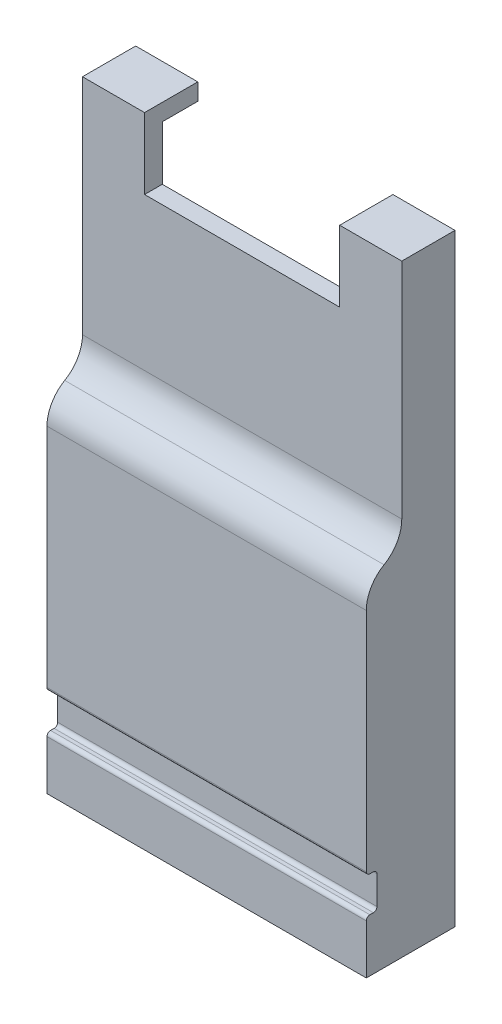
SolidWorks part; units mm, degrees
ref_plane "前视基准面" through (0, 0, 0) normal (0, 0, 1) x (1, 0, 0)
ref_plane "上视基准面" through (0, 0, 0) normal (0, 1, 0) x (1, 0, 0)
ref_plane "右视基准面" through (0, 0, 0) normal (1, 0, 0) x (0, 0, -1)
other "Configuration Table"
sketch "草图1" plane through (0, 0, 0) normal (0, 0, 1) x (1, 0, 0)
  line L1 (-45, -85) -> (45, -85)
  line L2 (-45, -85) -> (-45, 85)
  line L3 (-45, 85) -> (45, 85)
  line L4 (45, -85) -> (45, 85)
  line L5 (-45, -85) -> (45, 85) construction
  line L6 (-45, 85) -> (45, -85) construction
  point P0 (0, 0)
  dimension "D1" = 90
  dimension "D2" = 170
extrude "凸台-拉伸1" add sketch "草图1" along normal blind 25
sketch "草图2" plane through (0, 0, 25) normal (0, 0, 1) x (1, 0, 0)
  line L0 (-45, 85) -> (-45, -85) construction
  line L1 (45, 85) -> (-45, 85)
  line L2 (45, 85) -> (45, 14.7077)
  line L3 (45, 14.7077) -> (-45, 14.7077)
  line L4 (-45, 85) -> (-45, 14.7077)
extrude "切除-拉伸1" cut sketch "草图2" against normal blind 10
fillet "圆角1" radius 10 1 edges at (0, 14.7077, 25)
fillet "圆角2" radius 10 1 edges at (0, 14.7077, 15)
sketch "草图3" plane through (0, 0, 0) normal (0, 0, -1) x (-1, 0, 0)
  line L0 (45, 85) -> (45, -85) construction
  line L1 (-40.25, -85) -> (40.25, -85)
  line L2 (-40.25, -85) -> (-40.25, 80.25)
  line L3 (-40.25, 80.25) -> (40.25, 80.25)
  line L4 (40.25, -85) -> (40.25, 80.25)
  line L5 (45, -85) -> (-45, -85) construction
  point P0 (0, 0)
  point P6 (0, 0)
  point P7 (0, 0)
  point P10 (40.25, -85)
  dimension "D1" = 4.75
  dimension "D2" = 80.5
extrude "切除-拉伸2" cut sketch "草图3" against normal blind 10
sketch "草图5" plane through (40.25, 0, 0) normal (-1, 0, 0) x (0, 0, 1)
  line L0 (8.8, 80.25) -> (8.8, -85)
  line L3 (10, 80.25) -> (0, 80.25) construction
  line L4 (10, -85) -> (0, -85) construction
  line L5 (8.8, -85) -> (8.2, -85)
  line L6 (8.2, -85) -> (8.2, 80.25)
  line L7 (8.2, 80.25) -> (8.8, 80.25)
  line L8 (10, 80.25) -> (10, -85) construction
  dimension "D1" = 1.2
  dimension "D2" = 0.6
extrude "凸台-拉伸2" add sketch "草图5" along normal blind 0.9
sketch "草图6" plane through (-40.25, 0, 0) normal (1, 0, 0) x (0, 0, -1)
  line L0 (-8.8, 80.25) -> (-8.8, -85)
  line L3 (-9.4, -85) -> (-9.4, 80.25)
  line L4 (-9.4, 80.25) -> (-8.8, 80.25)
  line L5 (-10, -85) -> (-10, 80.25) construction
  line L6 (-9.4, -85) -> (-8.8, -85)
  dimension "D1" = 1.2
  dimension "D2" = 0.6
extrude "凸台-拉伸3" add sketch "草图6" along normal blind 0.9 contours L0 L6 L3 L4
sketch "草图9" plane through (0, 0, 25) normal (0, 0, 1) x (1, 0, 0)
  line L0 (-45, 4.7077) -> (-45, -85) construction
  line L1 (-45, -70.0642) -> (45, -70.0642)
  line L2 (-45, -70.0642) -> (-45, -60.0642)
  line L3 (-45, -60.0642) -> (45, -60.0642)
  line L4 (45, -70.0642) -> (45, -60.0642)
  line L5 (45, -85) -> (45, 4.7077) construction
  dimension "D1" = 10
extrude "切除-拉伸5" cut sketch "草图9" against normal blind 3
fillet "圆角8" radius 1 2 edges at (0, -60.0642, 22) (0, -60.0642, 25)
fillet "圆角9" radius 1 2 edges at (0, -70.0642, 25) (0, -70.0642, 22)
sketch "草图10" plane through (0, 0, 15) normal (0, 0, 1) x (1, 0, 0)
  line L0 (45, 85) -> (-45, 85) construction
  line L1 (-27.5, 105) -> (27.5, 105)
  line L2 (-27.5, 105) -> (-27.5, 65)
  line L3 (-27.5, 65) -> (27.5, 65)
  line L4 (27.5, 105) -> (27.5, 65)
  line L5 (-27.5, 105) -> (27.5, 65) construction
  line L6 (-27.5, 65) -> (27.5, 105) construction
  point P0 (0, 85)
  dimension "D1" = 55
  dimension "D2" = 40
extrude "切除-拉伸6" cut sketch "草图10" against normal blind 20
